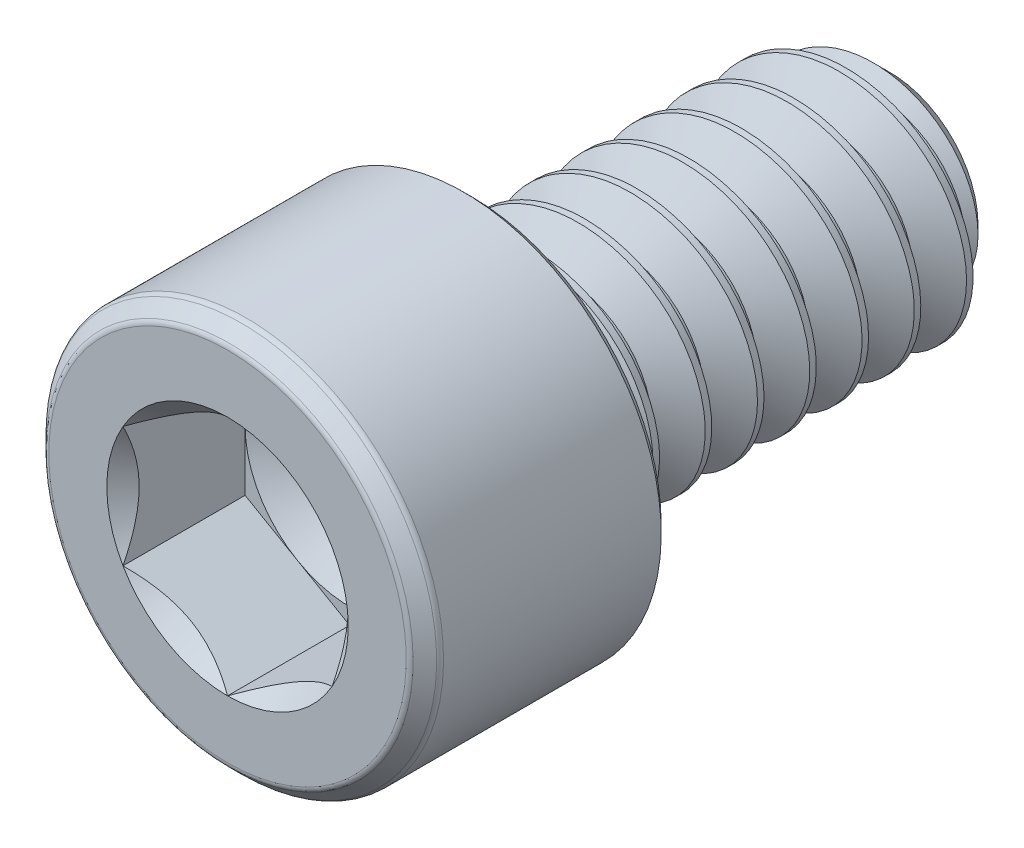
SolidWorks part; units mm, degrees
ref_plane "Front Plane" through (0, 0, 0) normal (0, 0, 1) x (1, 0, 0)
ref_plane "Top Plane" through (0, 0, 0) normal (0, 1, 0) x (1, 0, 0)
ref_plane "Right Plane" through (0, 0, 0) normal (1, 0, 0) x (0, 0, -1)
sketch "Sketch1" plane through (0, 0, 0) normal (1, 0, 0) x (0, 0, -1)
  line L0 (-2.5146, 0) -> (2.5146, 0) construction
  line L1 (-2.5146, 0) -> (-2.5146, 1.4986) construction
  line L2 (-2.5146, 1.4986) -> (-0.6604, 1.4986) construction
  line L3 (-0.6604, 1.4986) -> (-0.6604, 0.9271) construction
  line L4 (-0.6604, 0.9271) -> (2.2568, 0.9271) construction
  line L5 (2.4898, 0.9701) -> (2.6882, 0.6264) construction
  line L6 (2.6882, 0.6264) -> (2.8867, 0.9701) construction
  line L7 (2.8867, 0.9701) -> (2.4898, 0.9701) construction
  line L8 (2.2568, 0.9271) -> (2.5146, 0.6693) construction
  line L9 (2.5146, 0.6693) -> (2.5146, 0) construction
  line L10 (2.5146, 0.9271) -> (2.8619, 0.9271) construction
  line L11 (2.6882, 0.9701) -> (2.6882, 0.9271) construction
  line L12 (2.6882, 0.9271) -> (2.6882, 0.6693) construction
  line L13 (2.6882, 0.6693) -> (2.6882, 0.6264) construction
  line L14 (2.6634, 0.6693) -> (2.713, 0.6693) construction
  line L15 (2.5022, 0.9486) -> (2.8743, 0.9486) construction
  line L16 (2.713, 0.6693) -> (2.8743, 0.9486) construction
  line L17 (2.6634, 0.6693) -> (2.5022, 0.9486) construction
  line L18 (-2.5146, 0.7938) -> (-1.5875, 0.7938) construction
  line L19 (-1.5875, 0.7938) -> (-1.5875, 0) construction
  line L20 (1.1255, 0.9271) -> (1.1255, -0.9271) construction
  point P20 (2.6882, 0.9486)
  point P22 (1.1255, -0.9271)
  point P28 (1.1255, 0)
  point P29 (2.2568, -0.9271)
  point P30 (-1.124, 1.4986)
  point P31 (3.9751, 0)
  point P33 (-2.1209, 0)
  dimension "Length" = 3.175
  dimension "Head Height" = 1.8542
  dimension "D1" = 45
  dimension "Thread Pitch" = 0.3969
  dimension "D3" = 0.0496
  dimension "D4" = 1.3891
  dimension "D5" = 0.9271
  dimension "D2" = 1.3906
  dimension "Head Diameter" = 2.9972
  dimension "Drive Size" = 1.5875
  dimension "Screw Size Decimal Equivalent" = 1.8542
  dimension "D6" = 4.6355
  dimension "D7" = 4.6355
sketch "Sketch3" plane through (0, 0, 0) normal (1, 0, 0) x (0, 0, -1)
  line L0 (-2.5146, 1.357) -> (-2.5146, 0.7938)
  line L1 (-2.5146, 0.7938) -> (-1.5875, 0.7938)
  line L2 (-1.5875, 0.7938) -> (-1.5875, 0)
  line L3 (-1.5875, 0) -> (2.5146, 0)
  line L4 (2.5146, 0) -> (2.5146, 0.6693)
  line L5 (2.5146, 0.6693) -> (2.2568, 0.9271)
  line L6 (2.2568, 0.9271) -> (-0.5445, 0.9271)
  line L7 (-0.6604, 1.043) -> (-0.6604, 1.4387)
  line L8 (-0.7203, 1.4986) -> (-2.373, 1.4986)
  line L9 (-2.4992, 1.3941) -> (-2.4101, 1.4832)
  line L11 (-2.5146, 1.4986) -> (-0.6604, 1.4986) construction
  line L14 (-0.7203, 1.4986) -> (-0.6604, 1.4387)
  arc A0 (-2.4101, 1.4832) -> (-2.373, 1.4986) centre (-2.373, 1.4461) cw
  arc A1 (-2.4992, 1.3941) -> (-2.5146, 1.357) centre (-2.4621, 1.357) ccw
  arc A6 (-0.5445, 0.9271) -> (-0.6604, 1.043) centre (-0.5445, 1.043) cw
  point P25 (-2.5146, 1.3787)
  point P33 (-0.6604, 0.9271)
  dimension "D3" = 0.0525
  dimension "D10" = 0.1159
  dimension "D1" = 45
  dimension "D2" = 0.1199
  dimension "D7" = 45
  dimension "D8" = 0.0599
revolve "Revolve1" add sketch "Sketch3" angle 360 about L0
sketch "Sketch4" plane through (0, 0, 2.5146) normal (0, 0, 1) x (1, 0, 0)
  line L1 (0, 0.9165) -> (-0.7937, 0.4583)
  line L2 (-0.7937, 0.4583) -> (-0.7937, -0.4583)
  line L3 (-0.7937, -0.4583) -> (0, -0.9165)
  line L4 (0, -0.9165) -> (0.7937, -0.4583)
  line L5 (0.7937, -0.4583) -> (0.7937, 0.4583)
  line L6 (0.7937, 0.4583) -> (0, 0.9165)
  circle A0 centre (0, 0) radius 0.7937 construction
extrude "Cut-Extrude1" cut sketch "Sketch4" against normal up to vertex (0.9271 mm away) up to point (0, 0.7938, 1.5875)
sketch "Sketch5" plane through (0, 0, 2.5146) normal (0, 0, 1) x (1, 0, 0)
  circle A0 centre (0, 0) radius 0.9165
extrude "Cut-Extrude2" cut sketch "Sketch5" against normal up to next (0.9271 mm away) draft 45
sketch "Sketch10" plane through (0, 0, 1.5875) normal (0, 0, 1) x (1, 0, 0)
  line L0 (0.7937, 0.4583) -> (0.7937, -0.4583) construction
  circle A0 centre (0, 0) radius 0.7937
extrude "Cut-Extrude3" cut sketch "Sketch10" against normal through all draft 60
sketch "Sketch6" plane through (0, 0, -2.5146) normal (0, 0, -1) x (-1, 0, 0)
  circle A0 centre (0, 0) radius 0.9271 construction
  circle A1 centre (0, 0) radius 0.9271
curve "Helix/Spiral1" pitch 0.3969 height 3.5719 turns 9
ref_plane "Plane1" through (0, 0, 0.5445) normal (0, 0, 1) x (1, 0, 0)
split "Split1" trim tools "Plane1" bodies to split 112 resulting bodies 118 119
sketch "Sketch7" plane through (0, 0, 0) normal (1, 0, 0) x (0, 0, -1)
  line L0 (2.6634, 0.6693) -> (2.713, 0.6693)
  line L8 (2.5022, 0.9486) -> (2.8743, 0.9486)
  line L9 (2.8743, 0.9486) -> (2.713, 0.6693)
  line L11 (2.6634, 0.6693) -> (2.5022, 0.9486)
sweep "Cut-Sweep1" cut profiles "Sketch7" path "Helix/Spiral1" align with end faces yes
sketch "Sketch11" plane through (0, 0, 0) normal (1, 0, 0) x (0, 0, -1)
  line L2 (-0.6604, 0.9271) -> (2.2568, 0.9271) construction
  line L4 (-0.5445, 0.9271) -> (0.3826, 0)
  line L5 (-2.5146, 0) -> (2.5146, 0) construction
  line L9 (-1.1292, 0.9271) -> (-1.1292, 0)
  line L10 (-1.1292, 0) -> (0.3826, 0)
  line L12 (-1.1292, 0.9271) -> (-0.5445, 0.9271)
  dimension "D1" = 45
revolve "Revolve2" add sketch "Sketch11" angle 360 about L0
equation "\"D3@Sketch1\" = \"Thread Pitch@Sketch1\" / 8"
equation "\"D4@Sketch1\" = \"Thread Pitch@Sketch1\" * 3.5"
equation "\"D3@Helix/Spiral1\"=\"Length@Sketch1\" +( \"Thread Pitch@Sketch1\")"
equation "\"D4@Helix/Spiral1\" = \"Thread Pitch@Sketch1\""
equation "\"D5@Sketch1\"=\"Head Height@Sketch1\"*0.5"
equation "\"D2@Sketch3\"=\"Head Diameter@Sketch1\" /25"
equation "\"D3@Sketch3\"=\"D2@Sketch3\"*0.4375"
equation "\"D2@Sketch1\"=\"Head Height@Sketch1\"*0.75"
equation "\"D8@Sketch3\"=\"D2@Sketch3\"*0.5"
equation "\"D10@Sketch3\"=\"Screw Size Decimal Equivalent@Sketch1\"*0.0625"
equation "\"D7@Sketch1\"=\"Screw Size Decimal Equivalent@Sketch1\"*2.5"
equation "\"D6@Sketch1\"=\"D7@Sketch1\""
equation "\"D3@Sketch1\"=\"Thread Pitch@Sketch1\"/8"
